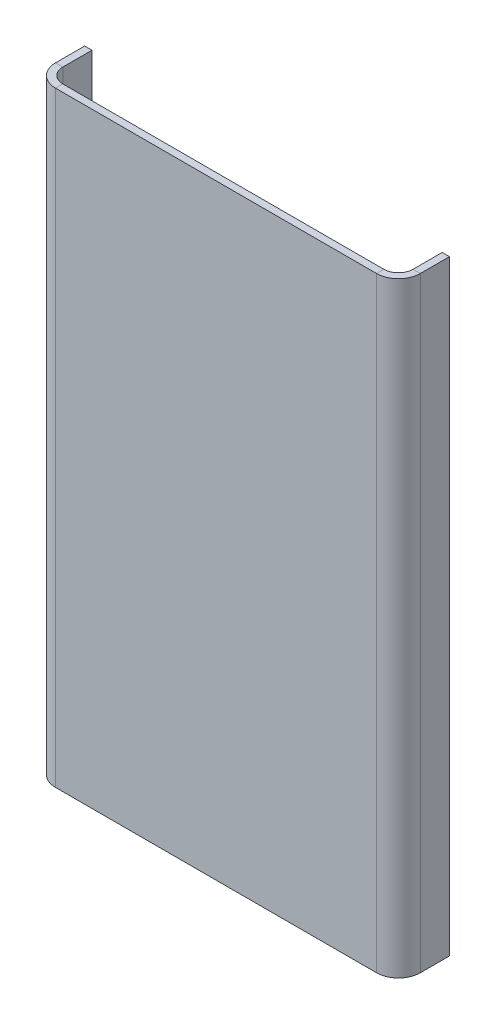
SolidWorks part; units mm, degrees
note: The reader was unsure of these and kept them because the rebuilt part matched: flange length of "Edge-Flange1".
material "ASTM A36 Steel"
ref_plane "Front Plane" through (0, 0, 0) normal (0, 0, 1) x (1, 0, 0)
ref_plane "Top Plane" through (0, 0, 0) normal (0, 1, 0) x (1, 0, 0)
ref_plane "Right Plane" through (0, 0, 0) normal (1, 0, 0) x (0, 0, -1)
sketch "Sketch1" plane through (0, 0, 0) normal (0, 0, 1) x (1, 0, 0)
  line L1 (-250, -415) -> (250, -415)
  line L2 (-250, -415) -> (-250, 415)
  line L3 (-250, 415) -> (250, 415)
  line L4 (250, -415) -> (250, 415)
  line L5 (-250, -415) -> (250, 415) construction
  line L6 (-250, 415) -> (250, -415) construction
  point P0 (0, 0)
  dimension "D1" = 500
  dimension "D2" = 830
base flange "Base-Flange1" sketch "Sketch1" thickness 10 reverse thickness direction no parameters "D1"=2.5
edge flange "Edge-Flange1" sketch "Sketch10" flange profiles "Sketch10", "Sketch11" flange angle 90 flange length 70 flange position material inside bend radius 20 thickness 10 relief rectangular parameters "D6"=10, "D8"=1
sketch "Sketch10" plane through (-250, 0, -10) normal (-1, 0, 0) x (0, 1, 0)
  line L0 (415, 0) -> (-415, 0) construction
  line L1 (415, 0) -> (-415, 0)
  line L2 (-415, 0) -> (-415, 60)
  line L3 (-415, 60) -> (415, 60)
  line L4 (415, 60) -> (415, 0)
sketch "Sketch11" plane through (250, 0, -10) normal (1, 0, 0) x (0, -1, 0)
  line L0 (415, 0) -> (-415, 0) construction
  line L1 (415, 0) -> (-415, 0)
  line L2 (-415, 0) -> (-415, 60)
  line L3 (-415, 60) -> (415, 60)
  line L4 (415, 60) -> (415, 0)
bend "EdgeBend1" bend radius 20 bend angle 90 parameters "D5"=1
bend "EdgeBend2" bend radius 20 bend angle 90 parameters "D5"=2
sketch "Bend-Lines1" [suppressed] plane through (0, 0, 0) normal (0, 1, 0) x (1, 0, 0)
sketch "Bounding-Box1" [suppressed] plane through (0, 0, 0) normal (0, 1, 0) x (1, 0, 0)
sheet metal parameters "Sheet-Metal2" thickness 10 parameters "D1"=2.5
flat pattern "Flat-Pattern2" [suppressed]
sketch "Bend-Lines2" plane through (0, 0, 0) normal (0, 1, 0) x (1, 0, 0)
sketch3d "Bounding-Box2" [suppressed]
  line L0 (-250, 415, 0) -> (-250, -415, 0) construction
  line L1 (250, 415, 0) -> (250, -415, 0) construction
  line L2 (-250, 415, 0) -> (250, 415, 0) construction
  line L3 (-250, -415, 0) -> (250, -415, 0) construction
sheet metal parameters "Sheet-Metal3" thickness 10 parameters "D1"=2.5
flat pattern "Flat-Pattern2"
sketch "Bend-Lines2" plane through (0, 0, 0) normal (0, 0, 1) x (1, 0, 0)
  line L0 (238.8496, -415) -> (238.8496, 415) construction
  line L1 (-238.8496, 415) -> (-238.8496, -415) construction
  line L2 (238.8496, -415) -> (238.8496, 415) construction
  line L3 (-238.8496, 415) -> (-238.8496, -415) construction
sketch3d "Bounding-Box2" [suppressed]
  line L0 (297.6991, 415, 0) -> (297.6991, -415, 0) construction
  line L1 (-297.6991, 415, 0) -> (-297.6991, -415, 0) construction
  line L2 (297.6991, 415, 0) -> (-297.6991, 415, 0) construction
  line L3 (297.6991, -415, 0) -> (-297.6991, -415, 0) construction
bend of the flat pattern "Flatten-<EdgeBend1>1"
bend of the flat pattern "Flatten-<EdgeBend2>1"
